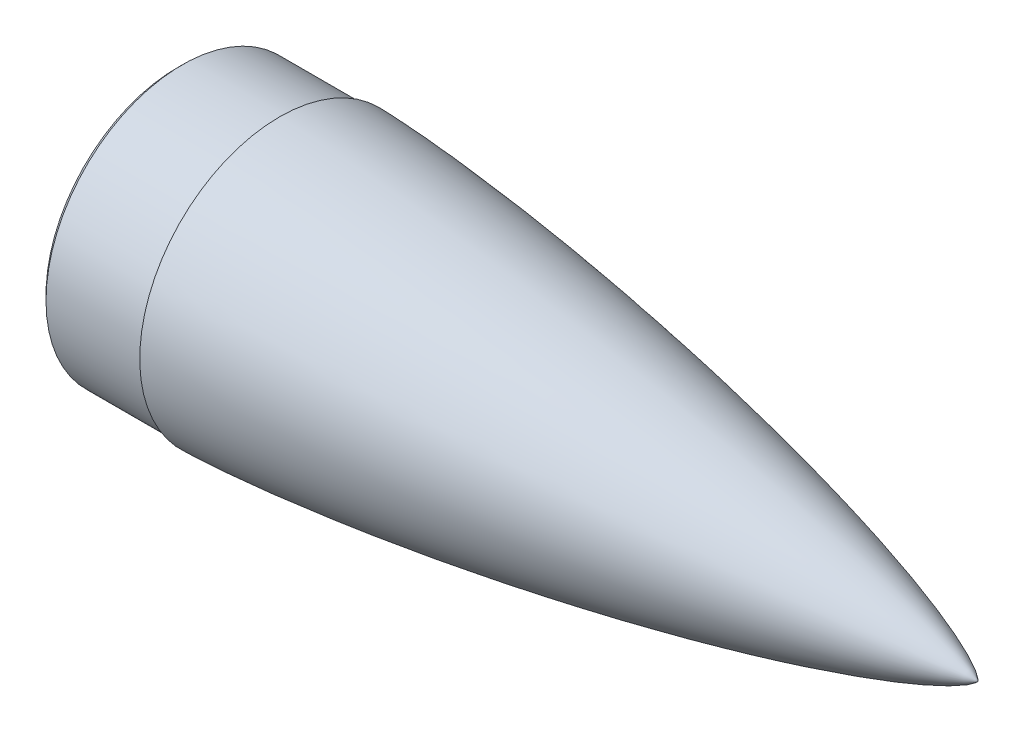
SolidWorks part; units mm, degrees
material "A-Glass Fiber"
ref_plane "Front Plane" through (0, 0, 0) normal (0, 0, 1) x (1, 0, 0)
ref_plane "Top Plane" through (0, 0, 0) normal (0, 1, 0) x (1, 0, 0)
ref_plane "Right Plane" through (0, 0, 0) normal (1, 0, 0) x (0, 0, -1)
ref_axis "Axis1" through (46.9179, 0, 0) along (-1, 0, 0)
sketch "Sketch10" plane through (0, 0, 0) normal (0, 0, 1) x (1, 0, 0)
  line L1 (0, 0) -> (486.9547, 0) construction
  line L3 (10.4058, 74) -> (-59.6047, 74)
  line L4 (410, 0) -> (370, 0)
  line L5 (-59.6047, 74) -> (-59.6047, 80)
  line L6 (-59.6047, 80) -> (0.3953, 80)
  line L7 (0.3953, 80) -> (0.3953, 82)
  spline S0 degree 4 poles (410, 0) (409.9975, 0.0135) (409.9903, 0.0398) (409.9682, 0.0901) (409.9228, 0.1731) (409.8557, 0.2738) (409.7494, 0.4128) (409.5865, 0.6001) (409.3278, 0.8643) (408.8869, 1.2618) (408.1308, 1.8624) (406.8022, 2.787) (404.4432, 4.2196) (400.2789, 6.4135) (393.3959, 9.5567) (381.5182, 14.281) (364.4202, 20.1562) (342.9172, 26.6587) (318.0464, 33.3763) (292.4185, 39.6708) (266.6767, 45.4808) (240.8439, 50.8699) (214.9342, 55.8756) (188.9575, 60.5206) (166.1751, 64.2782) (146.6128, 67.2799) (130.2888, 69.6317) (117.2166, 71.4213) (104.1318, 73.1159) (92.6717, 74.5119) (82.841, 75.6429) (74.6436, 76.5394) (68.0826, 77.2279) (61.5186, 77.8863) (54.9514, 78.513) (48.3811, 79.1063) (41.8077, 79.6639) (36.0532, 80.118) (31.1188, 80.4808) (27.0054, 80.764) (23.7139, 80.9783) (20.0971, 81.1993) (16.7286, 81.3888) (13.6086, 81.5486) (10.7374, 81.6811) (8.44, 81.7772) (6.1421, 81.8626) (4.1311, 81.9251) (2.4071, 81.9694) (1.2575, 81.9897) (0.6827, 81.9986) (0.3953, 82) knots 0 0 0 0 0 0.00013 0.00026 0.00052 0.0009 0.00128 0.001925 0.002882 0.004418 0.006927 0.011111 0.018279 0.030673 0.051704 0.083102 0.139909 0.202703 0.265496 0.32829 0.391083 0.453877 0.516671 0.579464 0.642258 0.673655 0.705051 0.736448 0.767845 0.799242 0.81494 0.830639 0.846337 0.862036 0.877734 0.893432 0.909131 0.924829 0.932678 0.940527 0.948377 0.956226 0.967169 0.972641 0.978113 0.983585 0.989056 0.994528 0.997264 1 1 1 1 1 construction
  spline S1 degree 4 poles (410, 0) (409.9975, 0.0135) (409.9903, 0.0398) (409.9682, 0.0901) (409.9228, 0.1731) (409.8557, 0.2738) (409.7494, 0.4128) (409.5865, 0.6001) (409.3278, 0.8643) (408.8869, 1.2618) (408.1308, 1.8624) (406.8022, 2.787) (404.4432, 4.2196) (400.2789, 6.4135) (393.3959, 9.5567) (381.5182, 14.281) (364.4202, 20.1562) (342.9172, 26.6587) (318.0464, 33.3763) (292.4185, 39.6708) (266.6767, 45.4808) (240.8439, 50.8699) (214.9342, 55.8756) (188.9575, 60.5206) (166.1751, 64.2782) (146.6128, 67.2799) (130.2888, 69.6317) (117.2166, 71.4213) (104.1318, 73.1159) (92.6717, 74.5119) (82.841, 75.6429) (74.6436, 76.5394) (68.0826, 77.2279) (61.5186, 77.8863) (54.9514, 78.513) (48.3811, 79.1063) (41.8077, 79.6639) (36.0532, 80.118) (31.1188, 80.4808) (27.0054, 80.764) (23.7139, 80.9783) (20.0971, 81.1993) (16.7286, 81.3888) (13.6086, 81.5486) (10.7374, 81.6811) (8.44, 81.7772) (6.1421, 81.8626) (4.1311, 81.9251) (2.4071, 81.9694) (1.2575, 81.9897) (0.6827, 81.9986) (0.3953, 82) knots 0 0 0 0 0 0.00013 0.00026 0.00052 0.0009 0.00128 0.001925 0.002882 0.004418 0.006927 0.011111 0.018279 0.030673 0.051704 0.083102 0.139909 0.202703 0.265496 0.32829 0.391083 0.453877 0.516671 0.579464 0.642258 0.673655 0.705051 0.736448 0.767845 0.799242 0.81494 0.830639 0.846337 0.862036 0.877734 0.893432 0.909131 0.924829 0.932678 0.940527 0.948377 0.956226 0.967169 0.972641 0.978113 0.983585 0.989056 0.994528 0.997264 1 1 1 1 1
  spline S2 degree 4 poles (370, 0) (369.9978, 0.0123) (369.9914, 0.0363) (369.9715, 0.0823) (369.9315, 0.1572) (369.8727, 0.2475) (369.7801, 0.3717) (369.6373, 0.5404) (369.4081, 0.7806) (369.0157, 1.1432) (368.3393, 1.6932) (367.1515, 2.5387) (365.0385, 3.8504) (361.3262, 5.8488) (355.2375, 8.6913) (344.7807, 12.9486) (329.7681, 18.2359) (310.9061, 24.0869) (289.0819, 30.1369) (266.5871, 35.8091) (243.9875, 41.0473) (221.3041, 45.9078) (198.5497, 50.424) (175.7335, 54.6161) (155.7206, 58.0081) (138.5346, 60.7184) (124.1925, 62.8423) (112.7069, 64.4586) (101.2096, 65.9893) (91.1393, 67.2504) (82.5004, 68.2722) (75.2966, 69.0822) (69.5307, 69.7042) (63.7619, 70.2991) (57.9902, 70.8653) (52.2156, 71.4013) (46.4381, 71.905) (41.3803, 72.3151) (37.0431, 72.6426) (33.4275, 72.8982) (30.5343, 73.0916) (27.3781, 73.2895) (23.9588, 73.4866) (20.7691, 73.6507) (17.8093, 73.7829) (15.3421, 73.8772) (13.6147, 73.9329) (12.1338, 73.9723) (11.1464, 73.9906) (10.6527, 73.9986) (10.4058, 74) knots 0 0 0 0 0 0.000135 0.00027 0.00054 0.00092 0.001299 0.001947 0.002931 0.004512 0.007081 0.01138 0.018708 0.031424 0.052705 0.084103 0.14091 0.203703 0.266497 0.329291 0.392084 0.454878 0.517672 0.580465 0.643259 0.674656 0.706052 0.737449 0.768846 0.800243 0.815941 0.831639 0.847338 0.863036 0.878735 0.894433 0.910132 0.92583 0.933679 0.941528 0.949378 0.957227 0.96792 0.978613 0.98396 0.989307 0.994653 0.997327 1 1 1 1 1 construction
  spline S3 degree 4 poles (370, 0) (369.9978, 0.0123) (369.9914, 0.0363) (369.9715, 0.0823) (369.9315, 0.1572) (369.8727, 0.2475) (369.7801, 0.3717) (369.6373, 0.5404) (369.4081, 0.7806) (369.0157, 1.1432) (368.3393, 1.6932) (367.1515, 2.5387) (365.0385, 3.8504) (361.3262, 5.8488) (355.2375, 8.6913) (344.7807, 12.9486) (329.7681, 18.2359) (310.9061, 24.0869) (289.0819, 30.1369) (266.5871, 35.8091) (243.9875, 41.0473) (221.3041, 45.9078) (198.5497, 50.424) (175.7335, 54.6161) (155.7206, 58.0081) (138.5346, 60.7184) (124.1925, 62.8423) (112.7069, 64.4586) (101.2096, 65.9893) (91.1393, 67.2504) (82.5004, 68.2722) (75.2966, 69.0822) (69.5307, 69.7042) (63.7619, 70.2991) (57.9902, 70.8653) (52.2156, 71.4013) (46.4381, 71.905) (41.3803, 72.3151) (37.0431, 72.6426) (33.4275, 72.8982) (30.5343, 73.0916) (27.3781, 73.2895) (23.9588, 73.4866) (20.7691, 73.6507) (17.8093, 73.7829) (15.3421, 73.8772) (13.6147, 73.9329) (12.1338, 73.9723) (11.1464, 73.9906) (10.6527, 73.9986) (10.4058, 74) knots 0 0 0 0 0 0.000135 0.00027 0.00054 0.00092 0.001299 0.001947 0.002931 0.004512 0.007081 0.01138 0.018708 0.031424 0.052705 0.084103 0.14091 0.203703 0.266497 0.329291 0.392084 0.454878 0.517672 0.580465 0.643259 0.674656 0.706052 0.737449 0.768846 0.800243 0.815941 0.831639 0.847338 0.863036 0.878735 0.894433 0.910132 0.92583 0.933679 0.941528 0.949378 0.957227 0.96792 0.978613 0.98396 0.989307 0.994653 0.997327 1 1 1 1 1
  point P7 (486.9547, 2.0902)
  point P13 (0, 0)
  dimension "D1" = 82
  dimension "D2" = 74
  dimension "D3" = 410
  dimension "D4" = 80
  dimension "D5" = 370
  dimension "D6" = 60
revolve "Revolve1" add sketch "Sketch10" angle 360 about axis through (46.9179, 0, 0) along (-1, 0, 0)
chamfer "Chamfer1" distance 3 angle 45 1 edges at (-59.6047, 0, -80)
